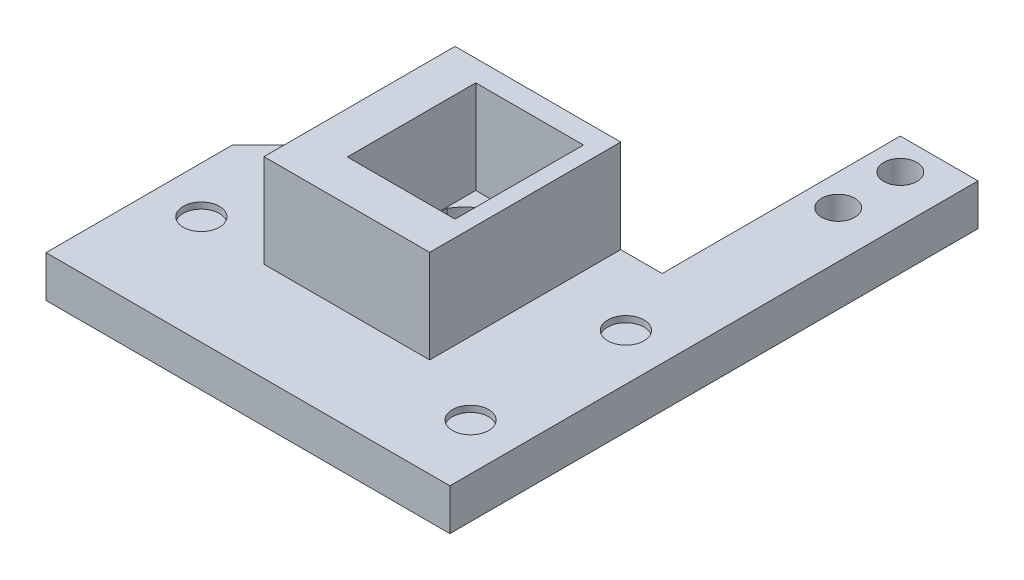
SolidWorks part; units mm, degrees
material "3D printed plastic"
ref_plane "Front Plane" through (0, 0, 0) normal (0, 0, 1) x (1, 0, 0)
ref_plane "Top Plane" through (0, 0, 0) normal (0, 1, 0) x (1, 0, 0)
ref_plane "Right Plane" through (0, 0, 0) normal (1, 0, 0) x (0, 0, -1)
sketch "Sketch1" plane through (0, 0, 0) normal (0, 1, 0) x (1, 0, 0)
  line L0 (-19.5, 14) -> (19.5, -14) construction
  line L1 (-19.5, -2) -> (7.5, -2) construction
  line L2 (7.5, -2) -> (7.5, 14) construction
  line L3 (-19.5, -14) -> (19.5, -14)
  line L4 (19.5, 14) -> (19.5, -14)
  line L5 (15, 7.5) -> (15, -7.5) construction
  line L6 (0, 0) -> (15, 0) construction
  line L7 (7.5, 14) -> (-19.5, 14)
  line L8 (-19.5, -14) -> (-19.5, -2)
  line L9 (0, 0) -> (-15, 0) construction
  line L10 (-19.5, 14) -> (-19.5, -2)
  line L12 (7.5, 14) -> (19.5, 14)
  line L13 (-15, 0) -> (-15, -3.5) construction
  circle A0 centre (-15, -3.5) radius 1.75
  circle A1 centre (15, -7.5) radius 1.75
  circle A2 centre (15, 7.5) radius 1.75
  dimension "D3" = 15
  dimension "D7" = 3.5
  dimension "D8" = 4
  dimension "D1" = 39
  dimension "D2" = 28
  dimension "D4" = 30
  dimension "D5" = 12
  dimension "D6" = 12
extrude "Boss-Extrude1" add sketch "Sketch1" against normal blind 4
sketch "Sketch3" plane through (0, 0, 0) normal (0, 1, 0) x (1, 0, 0)
  line L0 (-19.5, -14) -> (19.5, -14) construction
  line L1 (19.5, -14) -> (19.5, 14) construction
  line L2 (-3.85, 2.4034) -> (-3.85, 9.0966)
  line L3 (6.35, 2.4034) -> (6.35, 9.0966)
  arc A0 (6.35, 9.0966) -> (-3.85, 9.0966) centre (1.25, 5.75) ccw
  arc A1 (-3.85, 2.4034) -> (6.35, 2.4034) centre (1.25, 5.75) ccw
  dimension "D1" = 19.75
  dimension "D2" = 12.2
  dimension "D3" = 18.25
  dimension "D4" = 10.2
extrude "Cut-Extrude2" cut sketch "Sketch3" against normal through all
sketch "Sketch4" plane through (0, 0, 0) normal (0, 1, 0) x (1, 0, 0)
  line L0 (19.5, 14) -> (-19.5, 14) construction
  line L1 (12, 14) -> (19.5, 14)
  line L2 (12, 14) -> (12, 37)
  line L3 (12, 37) -> (19.5, 37)
  line L4 (19.5, 14) -> (19.5, 37)
  line L5 (19.5, -14) -> (19.5, 14) construction
  dimension "D1" = 23
  dimension "D2" = 7.5
extrude "Boss-Extrude2" add sketch "Sketch4" against normal up to surface (4 mm away) up to face at (1.25, -4, -5.75)
sketch "Sketch5" plane through (0, -4, 0) normal (0, -1, 0) x (1, 0, 0)
  line L1 (17.0496, 3.95) -> (19.0992, 7.5)
  line L2 (19.0992, 7.5) -> (17.0496, 11.05)
  line L3 (17.0496, 11.05) -> (12.9504, 11.05)
  line L4 (12.9504, 11.05) -> (10.9008, 7.5)
  line L5 (10.9008, 7.5) -> (12.9504, 3.95)
  line L6 (12.9504, 3.95) -> (17.0496, 3.95)
  line L7 (12.9504, -3.95) -> (10.9008, -7.5)
  line L8 (10.9008, -7.5) -> (12.9504, -11.05)
  line L9 (12.9504, -11.05) -> (17.0496, -11.05)
  line L10 (17.0496, -11.05) -> (19.0992, -7.5)
  line L11 (19.0992, -7.5) -> (17.0496, -3.95)
  line L12 (17.0496, -3.95) -> (12.9504, -3.95)
  line L13 (-12.9504, -0.05) -> (-10.9008, 3.5)
  line L14 (-10.9008, 3.5) -> (-12.9504, 7.05)
  line L15 (-12.9504, 7.05) -> (-17.0496, 7.05)
  line L16 (-17.0496, 7.05) -> (-19.0992, 3.5)
  line L17 (-19.0992, 3.5) -> (-17.0496, -0.05)
  line L18 (-17.0496, -0.05) -> (-12.9504, -0.05)
  circle A0 centre (15, 7.5) radius 3.55 construction
  circle A1 centre (15, -7.5) radius 3.55 construction
  circle A2 centre (-15, 3.5) radius 3.55 construction
  dimension "D1" = 7.1
extrude "Cut-Extrude3" cut sketch "Sketch5" against normal blind 3
sketch "Sketch6" plane through (0, -4, 0) normal (0, -1, 0) x (1, 0, 0)
  line L0 (15, -28) -> (15, -34) construction
  line L1 (15, -34) -> (15, -37) construction
  line L2 (12, -37) -> (19.5, -37) construction
  line L3 (12, -14) -> (12, -37) construction
  circle A0 centre (15, -34) radius 1.6
  circle A1 centre (15, -28) radius 1.6
  dimension "D1" = 3.2
  dimension "D2" = 3
  dimension "D3" = 6
  dimension "D4" = 3
extrude "Cut-Extrude4" cut sketch "Sketch6" against normal through all
sketch "Sketch8" plane through (0, -1, 0) normal (0, -1, 0) x (1, 0, 0)
  circle A0 centre (15, -7.5) radius 1.75
  circle A1 centre (15, 7.5) radius 1.75
  circle A2 centre (-15, 3.5) radius 1.75
  circle A3 centre (-15, 3.5) radius 1.75 construction
extrude "Boss-Extrude3" add sketch "Sketch8" against normal blind 0.4
sketch "Sketch9" plane through (0, 0, 0) normal (0, 1, 0) x (1, 0, 0)
  line L0 (12, 14) -> (-19.5, 14) construction
  line L1 (-3.95, 11.95) -> (6.45, 11.95)
  line L2 (-3.95, 11.95) -> (-3.95, -0.45)
  line L3 (-3.95, -0.45) -> (6.45, -0.45)
  line L4 (6.45, 11.95) -> (6.45, -0.45)
  line L5 (-8, 14) -> (8, 14)
  line L6 (-8, 14) -> (-8, -4.45)
  line L7 (-8, -4.45) -> (8, -4.45)
  line L8 (8, 14) -> (8, -4.45)
  line L9 (1.25, 5.75) -> (-3.95, 11.95) construction
  line L10 (1.25, 5.75) -> (6.45, -0.45) construction
  line L12 (1.25, 5.75) -> (1.25, 14) construction
  circle A0 centre (15, 7.5) radius 1.75 construction
  circle A1 centre (-15, -3.5) radius 1.75 construction
  dimension "D1" = 10.4
  dimension "D2" = 12.4
  dimension "D3" = 7
  dimension "D4" = 4
  dimension "D5" = 7
extrude "Boss-Extrude4" add sketch "Sketch9" along normal blind 9
chamfer "Chamfer1" distance 10 angle 45 1 edges at (-19.5, -2, -14)
